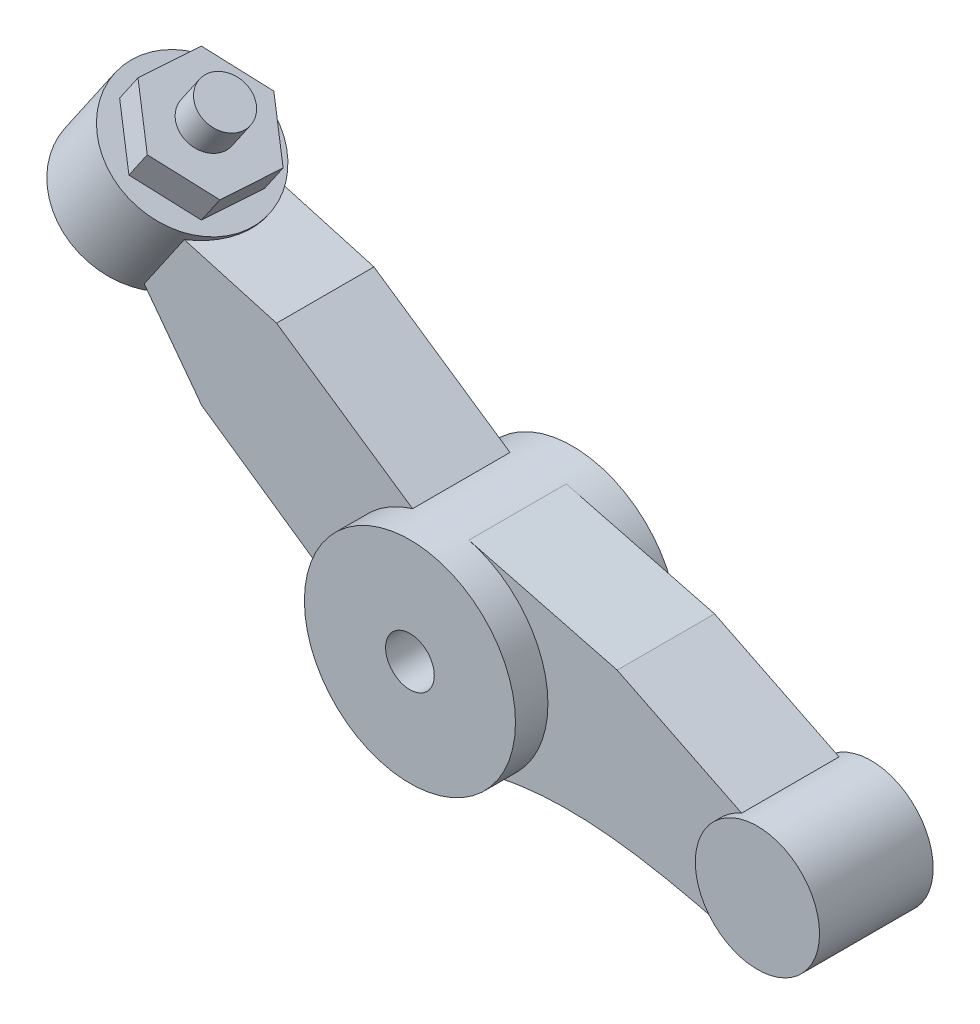
SolidWorks part; units mm, degrees
ref_plane "Front Plane" through (0, 0, 0) normal (0, 0, 1) x (1, 0, 0)
ref_plane "Top Plane" through (0, 0, 0) normal (0, 1, 0) x (1, 0, 0)
ref_plane "Right Plane" through (0, 0, 0) normal (1, 0, 0) x (0, 0, -1)
sketch "Sketch1" plane through (0, 0, 0) normal (0, 0, 1) x (1, 0, 0)
  line L0 (-2.1161, 0) -> (2.5863, 0) construction
  line L1 (0, 0) -> (0, 2.1278) construction
  line L2 (0, 0) -> (-3.6604, 2.5129) construction
  line L3 (0.326, 1.2585) -> (2.1523, 0.7854)
  line L4 (2.1523, 0.7854) -> (3.6857, 0.0261)
  line L5 (-3.468, 2.7932) -> (-3.8529, 2.2326)
  line L6 (-3.468, 2.7932) -> (-2.0428, 2.3884)
  line L7 (-2.0428, 2.3884) -> (-0.3675, 1.247)
  line L8 (-2.9629, 1.048) -> (-1.2957, -0.1051)
  line L9 (-3.8529, 2.2326) -> (-2.9629, 1.048)
  circle A0 centre (0, 0) radius 1.3
  circle A1 centre (0, 0) radius 0.3
  circle A2 centre (3.98, -0.68) radius 0.765
  spline S0 degree 3 poles (3.5799, -1.3321) (2.6515, -1.0862) (1.6701, -0.8839) (0.7091, -1.0896) knots 0 0 0 0 1 1 1 1
  point P15 (-2.3384, 2.5931)
  point P20 (-2.0428, 2.5129)
  point P25 (-2.0428, 2.3884)
  point P26 (2.1523, 0.7854)
  dimension "D1" = 2.6
  dimension "D2" = 0.6
  dimension "D3" = 1.53
  dimension "D4" = 0.68
  dimension "D5" = 3.98
  dimension "D6" = 4.44
  dimension "D7" = 0.68
  dimension "D8" = 0.82
  dimension "D9" = 34.47
extrude "Boss-Extrude1" add sketch "Sketch1" along normal mid plane 2 contours A0 A1 region at (0.999, 0.7732, 0)
extrude "Boss-Extrude2" add sketch "Sketch1<3>" along normal mid plane 1.4 separate body contours A2 region at (3.98, -0.68, 0)
sketch "Sketch1<3>" plane through (0, 0, 0) normal (0, 0, 1) x (1, 0, 0) same geometry as "Sketch1"
extrude "Boss-Extrude3" add sketch "Sketch1<4>" along normal mid plane 1.2 contours S0 A2 L4 L3 A0 region at (2.1681, -0.1643, 0)
sketch "Sketch1<4>" plane through (0, 0, 0) normal (0, 0, 1) x (1, 0, 0) same geometry as "Sketch1"
extrude "Boss-Extrude4" add sketch "Sketch1<5>" along normal mid plane 1.2 contours A0 L7 L6 L5 L9 L8 region at (-2.1884, 1.5023, 0)
sketch "Sketch1<5>" plane through (0, 0, 0) normal (0, 0, 1) x (1, 0, 0) same geometry as "Sketch1"
sketch "Sketch2" plane through (0, 0, 0) normal (0, 0, 1) x (1, 0, 0)
  line L0 (-3.8529, 2.2326) -> (-3.4454, 2.8262)
  line L1 (-3.4454, 2.8262) -> (-3.7751, 3.0526)
  line L2 (-3.7751, 3.0526) -> (-4.8378, 1.5047)
  line L3 (-4.3255, 1.9474) -> (-3.8529, 2.2326)
  line L4 (-3.468, 2.7932) -> (-3.8529, 2.2326) construction
  arc A0 (-4.8378, 1.5047) -> (-4.3255, 1.9474) centre (-4.6397, 1.7932) ccw
  point P8 (0, 0)
  point P10 (-4.2752, 2.0705)
  point P12 (0, 0)
  point P13 (0, 0)
  point P14 (-4.3646, 2.0097)
  dimension "D3" = 0.35
  dimension "D1" = 0.72
  dimension "D2" = 0.4
  dimension "D4" = 1
revolve "Revolve1" add sketch "Sketch2" angle 360 about L2
sketch "Sketch3" plane through (0, 0, 0) normal (0, 0, 1) x (1, 0, 0)
  line L0 (-3.6819, 3.1884) -> (-4.2932, 2.298)
  line L1 (-4.2932, 2.298) -> (-5.0434, 2.813)
  line L2 (-5.0434, 2.813) -> (-4.4322, 3.7034)
  line L3 (-4.4322, 3.7034) -> (-3.6819, 3.1884)
  line L6 (-4.5124, 2.6854) -> (-3.8529, 2.2326) construction
  line L7 (-4.1826, 2.459) -> (-4.1593, 2.4931) construction
  dimension "D1" = 0.91
  dimension "D2" = 1.08
revolve "Revolve2" add sketch "Sketch3" angle 360 about L0
sketch "Sketch4" plane through (0.3083, 0.449, 0) normal (0.566, 0.8244, 0) x (0.8244, -0.566, 0)
  line L1 (-4.2088, -0.406) -> (-4.1727, 0.3437)
  line L2 (-4.1727, 0.3437) -> (-4.804, 0.7497)
  line L3 (-4.804, 0.7497) -> (-5.4712, 0.406)
  line L4 (-5.4712, 0.406) -> (-5.5073, -0.3437)
  line L5 (-5.5073, -0.3437) -> (-4.876, -0.7497)
  line L6 (-4.876, -0.7497) -> (-4.2088, -0.406)
  circle A0 centre (-4.84, 0) radius 0.65 construction
  dimension "D1" = 1.3
extrude "Boss-Extrude5" add sketch "Sketch4" along normal blind 0.4 separate body
sketch "Sketch5" plane through (0.5347, 0.7788, 0) normal (0.566, 0.8244, 0) x (0.8244, -0.566, 0)
  circle A0 centre (-4.8601, -0.0312) radius 0.3
  dimension "D1" = 0.6
extrude "Boss-Extrude6" add sketch "Sketch5" along normal blind 0.4 separate body
